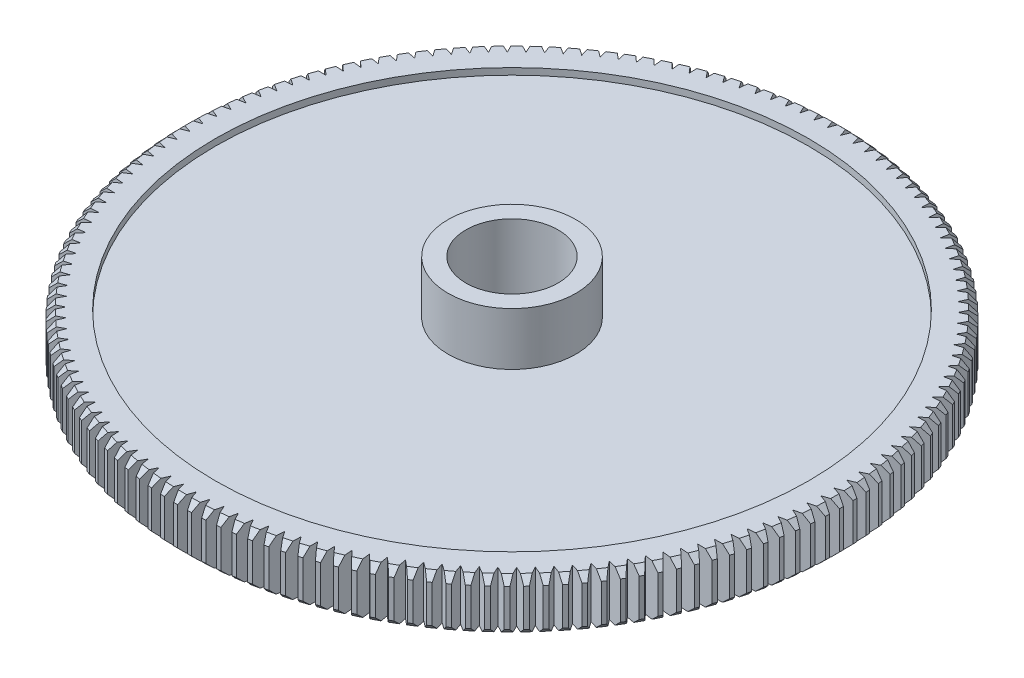
SolidWorks part; units mm, degrees
ref_plane "Спереди" through (0, 0, 0) normal (0, 0, 1) x (1, 0, 0)
ref_plane "Сверху" through (0, 0, 0) normal (0, 1, 0) x (1, 0, 0)
ref_plane "Справа" through (0, 0, 0) normal (1, 0, 0) x (0, 0, -1)
sketch "Эскиз1" plane through (0, 0, 0) normal (0, 1, 0) x (1, 0, 0)
  circle A0 centre (0, 0) radius 25
extrude "Вытянуть1" add sketch "Эскиз1" along normal blind 3.85
chamfer "Фаска2" distance 0.5 angle 45 1 edges at (0, 0, 25)
chamfer "Фаска1" distance 0.5 angle 45 1 edges at (0, 3.85, 25)
sketch "Эскиз2" plane through (0, 3.85, 0) normal (0, 1, 0) x (1, 0, 0)
  line L0 (0.5624, 25.354) -> (1.5615, 25.3121)
  line L1 (-0.5, 25.3553) -> (0.5, 25.3553)
  line L2 (-0.5, 25.3553) -> (0, 23.9335)
  line L3 (0, 23.9335) -> (0.5, 25.3553)
  line L4 (0.5624, 25.354) -> (1.0024, 23.9125)
  line L5 (1.0024, 23.9125) -> (1.5615, 25.3121)
  line L6 (1.6238, 25.3082) -> (2.6203, 25.2245)
  line L7 (1.6238, 25.3082) -> (2.0031, 23.8495)
  line L8 (2.0031, 23.8495) -> (2.6203, 25.2245)
  line L9 (2.6824, 25.218) -> (3.6745, 25.0926)
  line L10 (2.6824, 25.218) -> (3.0002, 23.7447)
  line L11 (3.0002, 23.7447) -> (3.6745, 25.0926)
  line L12 (3.7363, 25.0835) -> (4.7223, 24.9168)
  line L13 (3.7363, 25.0835) -> (3.9921, 23.5982)
  line L14 (3.9921, 23.5982) -> (4.7223, 24.9168)
  line L15 (4.7836, 24.9051) -> (5.7617, 24.6972)
  line L16 (4.7836, 24.9051) -> (4.977, 23.4103)
  line L17 (4.977, 23.4103) -> (5.7617, 24.6972)
  line L18 (5.8225, 24.6829) -> (6.7911, 24.4342)
  line L19 (5.8225, 24.6829) -> (5.9532, 23.1814)
  line L20 (5.9532, 23.1814) -> (6.7911, 24.4342)
  line L21 (6.8512, 24.4174) -> (7.8085, 24.1284)
  line L22 (6.8512, 24.4174) -> (6.9189, 22.9118)
  line L23 (6.9189, 22.9118) -> (7.8085, 24.1284)
  line L24 (7.8679, 24.1091) -> (8.8122, 23.7802)
  line L25 (7.8679, 24.1091) -> (7.8725, 22.6019)
  line L26 (7.8725, 22.6019) -> (8.8122, 23.7802)
  line L27 (8.8708, 23.7585) -> (9.8005, 23.3904)
  line L28 (8.8708, 23.7585) -> (8.8122, 22.2524)
  line L29 (8.8122, 22.2524) -> (9.8005, 23.3904)
  line L30 (9.8581, 23.3662) -> (10.7716, 22.9594)
  line L31 (9.8581, 23.3662) -> (9.7365, 21.8639)
  line L32 (9.7365, 21.8639) -> (10.7716, 22.9594)
  line L33 (10.8281, 22.9329) -> (11.7238, 22.4882)
  line L34 (10.8281, 22.9329) -> (10.6438, 21.437)
  line L35 (10.6438, 21.437) -> (11.7238, 22.4882)
  line L36 (11.7791, 22.4593) -> (12.6554, 21.9775)
  line L37 (11.7791, 22.4593) -> (11.5323, 20.9725)
  line L38 (11.5323, 20.9725) -> (12.6554, 21.9775)
  line L39 (12.7095, 21.9463) -> (13.5648, 21.4283)
  line L40 (12.7095, 21.9463) -> (12.4006, 20.4711)
  line L41 (12.4006, 20.4711) -> (13.5648, 21.4283)
  line L42 (13.6175, 21.3949) -> (14.4505, 20.8415)
  line L43 (13.6175, 21.3949) -> (13.2472, 19.9339)
  line L44 (13.2472, 19.9339) -> (14.4505, 20.8415)
  line L45 (14.5017, 20.8058) -> (15.3107, 20.2181)
  line L46 (14.5017, 20.8058) -> (14.0705, 19.3617)
  line L47 (14.0705, 19.3617) -> (15.3107, 20.2181)
  line L48 (15.3605, 20.1803) -> (16.1442, 19.5592)
  line L49 (15.3605, 20.1803) -> (14.8691, 18.7555)
  line L50 (14.8691, 18.7555) -> (16.1442, 19.5592)
  line L51 (16.1922, 19.5194) -> (16.9492, 18.866)
  line L52 (16.1922, 19.5194) -> (15.6417, 18.1164)
  line L53 (15.6417, 18.1164) -> (16.9492, 18.866)
  line L54 (16.9956, 18.8242) -> (17.7246, 18.1397)
  line L55 (16.9956, 18.8242) -> (16.3868, 17.4455)
  line L56 (16.3868, 17.4455) -> (17.7246, 18.1397)
  line L57 (17.7692, 18.096) -> (18.4689, 17.3815)
  line L58 (17.7692, 18.096) -> (17.1032, 16.7439)
  line L59 (17.1032, 16.7439) -> (18.4689, 17.3815)
  line L60 (18.5116, 17.336) -> (19.1807, 16.5929)
  line L61 (18.5116, 17.336) -> (17.7895, 16.013)
  line L62 (17.7895, 16.013) -> (19.1807, 16.5929)
  line L63 (19.2215, 16.5456) -> (19.8589, 15.7751)
  line L64 (19.2215, 16.5456) -> (18.4447, 15.254)
  line L65 (18.4447, 15.254) -> (19.8589, 15.7751)
  line L66 (19.8977, 15.7262) -> (20.5023, 14.9297)
  line L67 (19.8977, 15.7262) -> (19.0675, 14.4683)
  line L68 (19.0675, 14.4683) -> (20.5023, 14.9297)
  line L69 (20.539, 14.8792) -> (21.1097, 14.058)
  line L70 (20.539, 14.8792) -> (19.6568, 13.6571)
  line L71 (19.6568, 13.6571) -> (21.1097, 14.058)
  line L72 (21.1442, 14.006) -> (21.6801, 13.1617)
  line L73 (21.1442, 14.006) -> (20.2117, 12.822)
  line L74 (20.2117, 12.822) -> (21.6801, 13.1617)
  line L75 (21.7124, 13.1083) -> (22.2124, 12.2423)
  line L76 (21.7124, 13.1083) -> (20.7311, 11.9644)
  line L77 (20.7311, 11.9644) -> (22.2124, 12.2423)
  line L78 (22.2425, 12.1876) -> (22.7058, 11.3014)
  line L79 (22.2425, 12.1876) -> (21.2141, 11.0857)
  line L80 (21.2141, 11.0857) -> (22.7058, 11.3014)
  line L81 (22.7335, 11.2455) -> (23.1593, 10.3406)
  line L82 (22.7335, 11.2455) -> (21.6599, 10.1877)
  line L83 (21.6599, 10.1877) -> (23.1593, 10.3406)
  line L84 (23.1847, 10.2836) -> (23.5722, 9.3617)
  line L85 (23.1847, 10.2836) -> (22.0677, 9.2717)
  line L86 (22.0677, 9.2717) -> (23.5722, 9.3617)
  line L87 (23.5952, 9.3037) -> (23.9438, 8.3664)
  line L88 (23.5952, 9.3037) -> (22.4368, 8.3395)
  line L89 (22.4368, 8.3395) -> (23.9438, 8.3664)
  line L90 (23.9643, 8.3075) -> (24.2733, 7.3564)
  line L91 (23.9643, 8.3075) -> (22.7666, 7.3926)
  line L92 (22.7666, 7.3926) -> (24.2733, 7.3564)
  line L93 (24.2913, 7.2967) -> (24.5603, 6.3335)
  line L94 (24.2913, 7.2967) -> (23.0563, 6.4327)
  line L95 (23.0563, 6.4327) -> (24.5603, 6.3335)
  line L96 (24.5758, 6.2731) -> (24.8041, 5.2995)
  line L97 (24.5758, 6.2731) -> (23.3057, 5.4616)
  line L98 (23.3057, 5.4616) -> (24.8041, 5.2995)
  line L99 (24.8171, 5.2384) -> (25.0045, 4.2561)
  line L100 (24.8171, 5.2384) -> (23.5142, 4.4809)
  line L101 (23.5142, 4.4809) -> (25.0045, 4.2561)
  line L102 (25.0149, 4.1946) -> (25.161, 3.2053)
  line L103 (25.0149, 4.1946) -> (23.6814, 3.4922)
  line L104 (23.6814, 3.4922) -> (25.161, 3.2053)
  line L105 (25.1688, 3.1434) -> (25.2733, 2.1489)
  line L106 (25.1688, 3.1434) -> (23.807, 2.4975)
  line L107 (23.807, 2.4975) -> (25.2733, 2.1489)
  line L108 (25.2786, 2.0867) -> (25.3414, 1.0886)
  line L109 (25.2786, 2.0867) -> (23.8909, 1.4984)
  line L110 (23.8909, 1.4984) -> (25.3414, 1.0886)
  line L111 (25.344, 1.0263) -> (25.3649, 0.0265)
  line L112 (25.344, 1.0263) -> (23.9329, 0.4966)
  line L113 (23.9329, 0.4966) -> (25.3649, 0.0265)
  line L114 (25.3649, -0.0359) -> (25.344, -1.0357)
  line L115 (25.3649, -0.0359) -> (23.9329, -0.506)
  line L116 (23.9329, -0.506) -> (25.344, -1.0357)
  line L117 (25.3414, -1.0981) -> (25.2786, -2.0961)
  line L118 (25.3414, -1.0981) -> (23.8909, -1.5078)
  line L119 (23.8909, -1.5078) -> (25.2786, -2.0961)
  line L120 (25.2733, -2.1583) -> (25.1688, -3.1528)
  line L121 (25.2733, -2.1583) -> (23.807, -2.5069)
  line L122 (23.807, -2.5069) -> (25.1688, -3.1528)
  line L123 (25.161, -3.2147) -> (25.0149, -4.204)
  line L124 (25.161, -3.2147) -> (23.6814, -3.5017)
  line L125 (23.6814, -3.5017) -> (25.0149, -4.204)
  line L126 (25.0045, -4.2656) -> (24.8171, -5.2478)
  line L127 (25.0045, -4.2656) -> (23.5142, -4.4903)
  line L128 (23.5142, -4.4903) -> (24.8171, -5.2478)
  line L129 (24.8041, -5.3089) -> (24.5758, -6.2825)
  line L130 (24.8041, -5.3089) -> (23.3057, -5.471)
  line L131 (23.3057, -5.471) -> (24.5758, -6.2825)
  line L132 (24.5603, -6.3429) -> (24.2913, -7.3061)
  line L133 (24.5603, -6.3429) -> (23.0563, -6.4422)
  line L134 (23.0563, -6.4422) -> (24.2913, -7.3061)
  line L135 (24.2733, -7.3659) -> (23.9643, -8.3169)
  line L136 (24.2733, -7.3659) -> (22.7666, -7.402)
  line L137 (22.7666, -7.402) -> (23.9643, -8.3169)
  line L138 (23.9438, -8.3759) -> (23.5952, -9.3131)
  line L139 (23.9438, -8.3759) -> (22.4368, -8.3489)
  line L140 (22.4368, -8.3489) -> (23.5952, -9.3131)
  line L141 (23.5722, -9.3712) -> (23.1847, -10.293)
  line L142 (23.5722, -9.3712) -> (22.0677, -9.2811)
  line L143 (22.0677, -9.2811) -> (23.1847, -10.293)
  line L144 (23.1593, -10.3501) -> (22.7335, -11.2549)
  line L145 (23.1593, -10.3501) -> (21.6599, -10.1971)
  line L146 (21.6599, -10.1971) -> (22.7335, -11.2549)
  line L147 (22.7058, -11.3108) -> (22.2425, -12.197)
  line L148 (22.7058, -11.3108) -> (21.2141, -11.0952)
  line L149 (21.2141, -11.0952) -> (22.2425, -12.197)
  line L150 (22.2124, -12.2517) -> (21.7124, -13.1177)
  line L151 (22.2124, -12.2517) -> (20.7311, -11.9738)
  line L152 (20.7311, -11.9738) -> (21.7124, -13.1177)
  line L153 (21.6801, -13.1711) -> (21.1442, -14.0154)
  line L154 (21.6801, -13.1711) -> (20.2117, -12.8314)
  line L155 (20.2117, -12.8314) -> (21.1442, -14.0154)
  line L156 (21.1097, -14.0674) -> (20.539, -14.8886)
  line L157 (21.1097, -14.0674) -> (19.6568, -13.6666)
  line L158 (19.6568, -13.6666) -> (20.539, -14.8886)
  line L159 (20.5023, -14.9391) -> (19.8977, -15.7356)
  line L160 (20.5023, -14.9391) -> (19.0675, -14.4777)
  line L161 (19.0675, -14.4777) -> (19.8977, -15.7356)
  line L162 (19.8589, -15.7845) -> (19.2215, -16.555)
  line L163 (19.8589, -15.7845) -> (18.4447, -15.2635)
  line L164 (18.4447, -15.2635) -> (19.2215, -16.555)
  line L165 (19.1807, -16.6023) -> (18.5116, -17.3454)
  line L166 (19.1807, -16.6023) -> (17.7895, -16.0225)
  line L167 (17.7895, -16.0225) -> (18.5116, -17.3454)
  line L168 (18.4689, -17.3909) -> (17.7692, -18.1054)
  line L169 (18.4689, -17.3909) -> (17.1032, -16.7534)
  line L170 (17.1032, -16.7534) -> (17.7692, -18.1054)
  line L171 (17.7246, -18.1491) -> (16.9956, -18.8336)
  line L172 (17.7246, -18.1491) -> (16.3868, -17.4549)
  line L173 (16.3868, -17.4549) -> (16.9956, -18.8336)
  line L174 (16.9492, -18.8754) -> (16.1922, -19.5288)
  line L175 (16.9492, -18.8754) -> (15.6417, -18.1258)
  line L176 (15.6417, -18.1258) -> (16.1922, -19.5288)
  line L177 (16.1442, -19.5686) -> (15.3605, -20.1898)
  line L178 (16.1442, -19.5686) -> (14.8691, -18.7649)
  line L179 (14.8691, -18.7649) -> (15.3605, -20.1898)
  line L180 (15.3107, -20.2275) -> (14.5017, -20.8153)
  line L181 (15.3107, -20.2275) -> (14.0705, -19.3711)
  line L182 (14.0705, -19.3711) -> (14.5017, -20.8153)
  line L183 (14.4505, -20.8509) -> (13.6175, -21.4043)
  line L184 (14.4505, -20.8509) -> (13.2472, -19.9433)
  line L185 (13.2472, -19.9433) -> (13.6175, -21.4043)
  line L186 (13.5648, -21.4377) -> (12.7095, -21.9558)
  line L187 (13.5648, -21.4377) -> (12.4006, -20.4806)
  line L188 (12.4006, -20.4806) -> (12.7095, -21.9558)
  line L189 (12.6554, -21.987) -> (11.7791, -22.4687)
  line L190 (12.6554, -21.987) -> (11.5323, -20.9819)
  line L191 (11.5323, -20.9819) -> (11.7791, -22.4687)
  line L192 (11.7238, -22.4976) -> (10.8281, -22.9423)
  line L193 (11.7238, -22.4976) -> (10.6438, -21.4464)
  line L194 (10.6438, -21.4464) -> (10.8281, -22.9423)
  line L195 (10.7716, -22.9689) -> (9.8581, -23.3756)
  line L196 (10.7716, -22.9689) -> (9.7365, -21.8733)
  line L197 (9.7365, -21.8733) -> (9.8581, -23.3756)
  line L198 (9.8005, -23.3998) -> (8.8708, -23.7679)
  line L199 (9.8005, -23.3998) -> (8.8122, -22.2619)
  line L200 (8.8122, -22.2619) -> (8.8708, -23.7679)
  line L201 (8.8122, -23.7897) -> (7.8679, -24.1185)
  line L202 (8.8122, -23.7897) -> (7.8725, -22.6114)
  line L203 (7.8725, -22.6114) -> (7.8679, -24.1185)
  line L204 (7.8085, -24.1378) -> (6.8512, -24.4269)
  line L205 (7.8085, -24.1378) -> (6.9189, -22.9212)
  line L206 (6.9189, -22.9212) -> (6.8512, -24.4269)
  line L207 (6.7911, -24.4436) -> (5.8225, -24.6923)
  line L208 (6.7911, -24.4436) -> (5.9532, -23.1908)
  line L209 (5.9532, -23.1908) -> (5.8225, -24.6923)
  line L210 (5.7617, -24.7066) -> (4.7836, -24.9145)
  line L211 (5.7617, -24.7066) -> (4.977, -23.4198)
  line L212 (4.977, -23.4198) -> (4.7836, -24.9145)
  line L213 (4.7223, -24.9262) -> (3.7363, -25.093)
  line L214 (4.7223, -24.9262) -> (3.9921, -23.6077)
  line L215 (3.9921, -23.6077) -> (3.7363, -25.093)
  line L216 (3.6745, -25.1021) -> (2.6824, -25.2274)
  line L217 (3.6745, -25.1021) -> (3.0002, -23.7541)
  line L218 (3.0002, -23.7541) -> (2.6824, -25.2274)
  line L219 (2.6203, -25.2339) -> (1.6238, -25.3176)
  line L220 (2.6203, -25.2339) -> (2.0031, -23.8589)
  line L221 (2.0031, -23.8589) -> (1.6238, -25.3176)
  line L222 (1.5615, -25.3215) -> (0.5624, -25.3634)
  line L223 (1.5615, -25.3215) -> (1.0024, -23.9219)
  line L224 (1.0024, -23.9219) -> (0.5624, -25.3634)
  line L225 (0.5, -25.3647) -> (-0.5, -25.3647)
  line L226 (0.5, -25.3647) -> (0, -23.9429)
  line L227 (0, -23.9429) -> (-0.5, -25.3647)
  line L228 (-0.5624, -25.3634) -> (-1.5615, -25.3215)
  line L229 (-0.5624, -25.3634) -> (-1.0024, -23.9219)
  line L230 (-1.0024, -23.9219) -> (-1.5615, -25.3215)
  line L231 (-1.6238, -25.3176) -> (-2.6203, -25.2339)
  line L232 (-1.6238, -25.3176) -> (-2.0031, -23.8589)
  line L233 (-2.0031, -23.8589) -> (-2.6203, -25.2339)
  line L234 (-2.6824, -25.2274) -> (-3.6745, -25.1021)
  line L235 (-2.6824, -25.2274) -> (-3.0002, -23.7541)
  line L236 (-3.0002, -23.7541) -> (-3.6745, -25.1021)
  line L237 (-3.7363, -25.093) -> (-4.7223, -24.9262)
  line L238 (-3.7363, -25.093) -> (-3.9921, -23.6077)
  line L239 (-3.9921, -23.6077) -> (-4.7223, -24.9262)
  line L240 (-4.7836, -24.9145) -> (-5.7617, -24.7066)
  line L241 (-4.7836, -24.9145) -> (-4.977, -23.4198)
  line L242 (-4.977, -23.4198) -> (-5.7617, -24.7066)
  line L243 (-5.8225, -24.6923) -> (-6.7911, -24.4436)
  line L244 (-5.8225, -24.6923) -> (-5.9532, -23.1908)
  line L245 (-5.9532, -23.1908) -> (-6.7911, -24.4436)
  line L246 (-6.8512, -24.4269) -> (-7.8085, -24.1378)
  line L247 (-6.8512, -24.4269) -> (-6.9189, -22.9212)
  line L248 (-6.9189, -22.9212) -> (-7.8085, -24.1378)
  line L249 (-7.8679, -24.1185) -> (-8.8122, -23.7897)
  line L250 (-7.8679, -24.1185) -> (-7.8725, -22.6114)
  line L251 (-7.8725, -22.6114) -> (-8.8122, -23.7897)
  line L252 (-8.8708, -23.7679) -> (-9.8005, -23.3998)
  line L253 (-8.8708, -23.7679) -> (-8.8122, -22.2619)
  line L254 (-8.8122, -22.2619) -> (-9.8005, -23.3998)
  line L255 (-9.8581, -23.3756) -> (-10.7716, -22.9689)
  line L256 (-9.8581, -23.3756) -> (-9.7365, -21.8733)
  line L257 (-9.7365, -21.8733) -> (-10.7716, -22.9689)
  line L258 (-10.8281, -22.9423) -> (-11.7238, -22.4976)
  line L259 (-10.8281, -22.9423) -> (-10.6438, -21.4464)
  line L260 (-10.6438, -21.4464) -> (-11.7238, -22.4976)
  line L261 (-11.7791, -22.4687) -> (-12.6554, -21.987)
  line L262 (-11.7791, -22.4687) -> (-11.5323, -20.9819)
  line L263 (-11.5323, -20.9819) -> (-12.6554, -21.987)
  line L264 (-12.7095, -21.9558) -> (-13.5648, -21.4377)
  line L265 (-12.7095, -21.9558) -> (-12.4006, -20.4806)
  line L266 (-12.4006, -20.4806) -> (-13.5648, -21.4377)
  line L267 (-13.6175, -21.4043) -> (-14.4505, -20.8509)
  line L268 (-13.6175, -21.4043) -> (-13.2472, -19.9433)
  line L269 (-13.2472, -19.9433) -> (-14.4505, -20.8509)
  line L270 (-14.5017, -20.8153) -> (-15.3107, -20.2275)
  line L271 (-14.5017, -20.8153) -> (-14.0705, -19.3711)
  line L272 (-14.0705, -19.3711) -> (-15.3107, -20.2275)
  line L273 (-15.3605, -20.1898) -> (-16.1442, -19.5686)
  line L274 (-15.3605, -20.1898) -> (-14.8691, -18.7649)
  line L275 (-14.8691, -18.7649) -> (-16.1442, -19.5686)
  line L276 (-16.1922, -19.5288) -> (-16.9492, -18.8754)
  line L277 (-16.1922, -19.5288) -> (-15.6417, -18.1258)
  line L278 (-15.6417, -18.1258) -> (-16.9492, -18.8754)
  line L279 (-16.9956, -18.8336) -> (-17.7246, -18.1491)
  line L280 (-16.9956, -18.8336) -> (-16.3868, -17.4549)
  line L281 (-16.3868, -17.4549) -> (-17.7246, -18.1491)
  line L282 (-17.7692, -18.1054) -> (-18.4689, -17.3909)
  line L283 (-17.7692, -18.1054) -> (-17.1032, -16.7534)
  line L284 (-17.1032, -16.7534) -> (-18.4689, -17.3909)
  line L285 (-18.5116, -17.3454) -> (-19.1807, -16.6023)
  line L286 (-18.5116, -17.3454) -> (-17.7895, -16.0225)
  line L287 (-17.7895, -16.0225) -> (-19.1807, -16.6023)
  line L288 (-19.2215, -16.555) -> (-19.8589, -15.7845)
  line L289 (-19.2215, -16.555) -> (-18.4447, -15.2635)
  line L290 (-18.4447, -15.2635) -> (-19.8589, -15.7845)
  line L291 (-19.8977, -15.7356) -> (-20.5023, -14.9391)
  line L292 (-19.8977, -15.7356) -> (-19.0675, -14.4777)
  line L293 (-19.0675, -14.4777) -> (-20.5023, -14.9391)
  line L294 (-20.539, -14.8886) -> (-21.1097, -14.0674)
  line L295 (-20.539, -14.8886) -> (-19.6568, -13.6666)
  line L296 (-19.6568, -13.6666) -> (-21.1097, -14.0674)
  line L297 (-21.1442, -14.0154) -> (-21.6801, -13.1711)
  line L298 (-21.1442, -14.0154) -> (-20.2117, -12.8314)
  line L299 (-20.2117, -12.8314) -> (-21.6801, -13.1711)
  line L300 (-21.7124, -13.1177) -> (-22.2124, -12.2517)
  line L301 (-21.7124, -13.1177) -> (-20.7311, -11.9738)
  line L302 (-20.7311, -11.9738) -> (-22.2124, -12.2517)
  line L303 (-22.2425, -12.197) -> (-22.7058, -11.3108)
  line L304 (-22.2425, -12.197) -> (-21.2141, -11.0952)
  line L305 (-21.2141, -11.0952) -> (-22.7058, -11.3108)
  line L306 (-22.7335, -11.2549) -> (-23.1593, -10.3501)
  line L307 (-22.7335, -11.2549) -> (-21.6599, -10.1971)
  line L308 (-21.6599, -10.1971) -> (-23.1593, -10.3501)
  line L309 (-23.1847, -10.293) -> (-23.5722, -9.3712)
  line L310 (-23.1847, -10.293) -> (-22.0677, -9.2811)
  line L311 (-22.0677, -9.2811) -> (-23.5722, -9.3712)
  line L312 (-23.5952, -9.3131) -> (-23.9438, -8.3759)
  line L313 (-23.5952, -9.3131) -> (-22.4368, -8.3489)
  line L314 (-22.4368, -8.3489) -> (-23.9438, -8.3759)
  line L315 (-23.9643, -8.3169) -> (-24.2733, -7.3659)
  line L316 (-23.9643, -8.3169) -> (-22.7666, -7.402)
  line L317 (-22.7666, -7.402) -> (-24.2733, -7.3659)
  line L318 (-24.2913, -7.3061) -> (-24.5603, -6.3429)
  line L319 (-24.2913, -7.3061) -> (-23.0563, -6.4422)
  line L320 (-23.0563, -6.4422) -> (-24.5603, -6.3429)
  line L321 (-24.5758, -6.2825) -> (-24.8041, -5.3089)
  line L322 (-24.5758, -6.2825) -> (-23.3057, -5.471)
  line L323 (-23.3057, -5.471) -> (-24.8041, -5.3089)
  line L324 (-24.8171, -5.2478) -> (-25.0045, -4.2656)
  line L325 (-24.8171, -5.2478) -> (-23.5142, -4.4903)
  line L326 (-23.5142, -4.4903) -> (-25.0045, -4.2656)
  line L327 (-25.0149, -4.204) -> (-25.161, -3.2147)
  line L328 (-25.0149, -4.204) -> (-23.6814, -3.5017)
  line L329 (-23.6814, -3.5017) -> (-25.161, -3.2147)
  line L330 (-25.1688, -3.1528) -> (-25.2733, -2.1583)
  line L331 (-25.1688, -3.1528) -> (-23.807, -2.5069)
  line L332 (-23.807, -2.5069) -> (-25.2733, -2.1583)
  line L333 (-25.2786, -2.0961) -> (-25.3414, -1.0981)
  line L334 (-25.2786, -2.0961) -> (-23.8909, -1.5078)
  line L335 (-23.8909, -1.5078) -> (-25.3414, -1.0981)
  line L336 (-25.344, -1.0357) -> (-25.3649, -0.0359)
  line L337 (-25.344, -1.0357) -> (-23.9329, -0.506)
  line L338 (-23.9329, -0.506) -> (-25.3649, -0.0359)
  line L339 (-25.3649, 0.0265) -> (-25.344, 1.0263)
  line L340 (-25.3649, 0.0265) -> (-23.9329, 0.4966)
  line L341 (-23.9329, 0.4966) -> (-25.344, 1.0263)
  line L342 (-25.3414, 1.0886) -> (-25.2786, 2.0867)
  line L343 (-25.3414, 1.0886) -> (-23.8909, 1.4984)
  line L344 (-23.8909, 1.4984) -> (-25.2786, 2.0867)
  line L345 (-25.2733, 2.1489) -> (-25.1688, 3.1434)
  line L346 (-25.2733, 2.1489) -> (-23.807, 2.4975)
  line L347 (-23.807, 2.4975) -> (-25.1688, 3.1434)
  line L348 (-25.161, 3.2053) -> (-25.0149, 4.1946)
  line L349 (-25.161, 3.2053) -> (-23.6814, 3.4922)
  line L350 (-23.6814, 3.4922) -> (-25.0149, 4.1946)
  line L351 (-25.0045, 4.2561) -> (-24.8171, 5.2384)
  line L352 (-25.0045, 4.2561) -> (-23.5142, 4.4809)
  line L353 (-23.5142, 4.4809) -> (-24.8171, 5.2384)
  line L354 (-24.8041, 5.2995) -> (-24.5758, 6.2731)
  line L355 (-24.8041, 5.2995) -> (-23.3057, 5.4616)
  line L356 (-23.3057, 5.4616) -> (-24.5758, 6.2731)
  line L357 (-24.5603, 6.3335) -> (-24.2913, 7.2967)
  line L358 (-24.5603, 6.3335) -> (-23.0563, 6.4327)
  line L359 (-23.0563, 6.4327) -> (-24.2913, 7.2967)
  line L360 (-24.2733, 7.3564) -> (-23.9643, 8.3075)
  line L361 (-24.2733, 7.3564) -> (-22.7666, 7.3926)
  line L362 (-22.7666, 7.3926) -> (-23.9643, 8.3075)
  line L363 (-23.9438, 8.3664) -> (-23.5952, 9.3037)
  line L364 (-23.9438, 8.3664) -> (-22.4368, 8.3395)
  line L365 (-22.4368, 8.3395) -> (-23.5952, 9.3037)
  line L366 (-23.5722, 9.3617) -> (-23.1847, 10.2836)
  line L367 (-23.5722, 9.3617) -> (-22.0677, 9.2717)
  line L368 (-22.0677, 9.2717) -> (-23.1847, 10.2836)
  line L369 (-23.1593, 10.3406) -> (-22.7335, 11.2455)
  line L370 (-23.1593, 10.3406) -> (-21.6599, 10.1877)
  line L371 (-21.6599, 10.1877) -> (-22.7335, 11.2455)
  line L372 (-22.7058, 11.3014) -> (-22.2425, 12.1876)
  line L373 (-22.7058, 11.3014) -> (-21.2141, 11.0857)
  line L374 (-21.2141, 11.0857) -> (-22.2425, 12.1876)
  line L375 (-22.2124, 12.2423) -> (-21.7124, 13.1083)
  line L376 (-22.2124, 12.2423) -> (-20.7311, 11.9644)
  line L377 (-20.7311, 11.9644) -> (-21.7124, 13.1083)
  line L378 (-21.6801, 13.1617) -> (-21.1442, 14.006)
  line L379 (-21.6801, 13.1617) -> (-20.2117, 12.822)
  line L380 (-20.2117, 12.822) -> (-21.1442, 14.006)
  line L381 (-21.1097, 14.058) -> (-20.539, 14.8792)
  line L382 (-21.1097, 14.058) -> (-19.6568, 13.6571)
  line L383 (-19.6568, 13.6571) -> (-20.539, 14.8792)
  line L384 (-20.5023, 14.9297) -> (-19.8977, 15.7262)
  line L385 (-20.5023, 14.9297) -> (-19.0675, 14.4683)
  line L386 (-19.0675, 14.4683) -> (-19.8977, 15.7262)
  line L387 (-19.8589, 15.7751) -> (-19.2215, 16.5456)
  line L388 (-19.8589, 15.7751) -> (-18.4447, 15.254)
  line L389 (-18.4447, 15.254) -> (-19.2215, 16.5456)
  line L390 (-19.1807, 16.5929) -> (-18.5116, 17.336)
  line L391 (-19.1807, 16.5929) -> (-17.7895, 16.013)
  line L392 (-17.7895, 16.013) -> (-18.5116, 17.336)
  line L393 (-18.4689, 17.3815) -> (-17.7692, 18.096)
  line L394 (-18.4689, 17.3815) -> (-17.1032, 16.7439)
  line L395 (-17.1032, 16.7439) -> (-17.7692, 18.096)
  line L396 (-17.7246, 18.1397) -> (-16.9956, 18.8242)
  line L397 (-17.7246, 18.1397) -> (-16.3868, 17.4455)
  line L398 (-16.3868, 17.4455) -> (-16.9956, 18.8242)
  line L399 (-16.9492, 18.866) -> (-16.1922, 19.5194)
  line L400 (-16.9492, 18.866) -> (-15.6417, 18.1164)
  line L401 (-15.6417, 18.1164) -> (-16.1922, 19.5194)
  line L402 (-16.1442, 19.5592) -> (-15.3605, 20.1803)
  line L403 (-16.1442, 19.5592) -> (-14.8691, 18.7555)
  line L404 (-14.8691, 18.7555) -> (-15.3605, 20.1803)
  line L405 (-15.3107, 20.2181) -> (-14.5017, 20.8058)
  line L406 (-15.3107, 20.2181) -> (-14.0705, 19.3617)
  line L407 (-14.0705, 19.3617) -> (-14.5017, 20.8058)
  line L408 (-14.4505, 20.8415) -> (-13.6175, 21.3949)
  line L409 (-14.4505, 20.8415) -> (-13.2472, 19.9339)
  line L410 (-13.2472, 19.9339) -> (-13.6175, 21.3949)
  line L411 (-13.5648, 21.4283) -> (-12.7095, 21.9463)
  line L412 (-13.5648, 21.4283) -> (-12.4006, 20.4711)
  line L413 (-12.4006, 20.4711) -> (-12.7095, 21.9463)
  line L414 (-12.6554, 21.9775) -> (-11.7791, 22.4593)
  line L415 (-12.6554, 21.9775) -> (-11.5323, 20.9725)
  line L416 (-11.5323, 20.9725) -> (-11.7791, 22.4593)
  line L417 (-11.7238, 22.4882) -> (-10.8281, 22.9329)
  line L418 (-11.7238, 22.4882) -> (-10.6438, 21.437)
  line L419 (-10.6438, 21.437) -> (-10.8281, 22.9329)
  line L420 (-10.7716, 22.9594) -> (-9.8581, 23.3662)
  line L421 (-10.7716, 22.9594) -> (-9.7365, 21.8639)
  line L422 (-9.7365, 21.8639) -> (-9.8581, 23.3662)
  line L423 (-9.8005, 23.3904) -> (-8.8708, 23.7585)
  line L424 (-9.8005, 23.3904) -> (-8.8122, 22.2524)
  line L425 (-8.8122, 22.2524) -> (-8.8708, 23.7585)
  line L426 (-8.8122, 23.7802) -> (-7.8679, 24.1091)
  line L427 (-8.8122, 23.7802) -> (-7.8725, 22.6019)
  line L428 (-7.8725, 22.6019) -> (-7.8679, 24.1091)
  line L429 (-7.8085, 24.1284) -> (-6.8512, 24.4174)
  line L430 (-7.8085, 24.1284) -> (-6.9189, 22.9118)
  line L431 (-6.9189, 22.9118) -> (-6.8512, 24.4174)
  line L432 (-6.7911, 24.4342) -> (-5.8225, 24.6829)
  line L433 (-6.7911, 24.4342) -> (-5.9532, 23.1814)
  line L434 (-5.9532, 23.1814) -> (-5.8225, 24.6829)
  line L435 (-5.7617, 24.6972) -> (-4.7836, 24.9051)
  line L436 (-5.7617, 24.6972) -> (-4.977, 23.4103)
  line L437 (-4.977, 23.4103) -> (-4.7836, 24.9051)
  line L438 (-4.7223, 24.9168) -> (-3.7363, 25.0835)
  line L439 (-4.7223, 24.9168) -> (-3.9921, 23.5982)
  line L440 (-3.9921, 23.5982) -> (-3.7363, 25.0835)
  line L441 (-3.6745, 25.0926) -> (-2.6824, 25.218)
  line L442 (-3.6745, 25.0926) -> (-3.0002, 23.7447)
  line L443 (-3.0002, 23.7447) -> (-2.6824, 25.218)
  line L444 (-2.6203, 25.2245) -> (-1.6238, 25.3082)
  line L445 (-2.6203, 25.2245) -> (-2.0031, 23.8495)
  line L446 (-2.0031, 23.8495) -> (-1.6238, 25.3082)
  line L447 (-1.5615, 25.3121) -> (-0.5624, 25.354)
  line L448 (-1.5615, 25.3121) -> (-1.0024, 23.9125)
  line L449 (-1.0024, 23.9125) -> (-0.5624, 25.354)
extrude "Вытянуть2" cut sketch "Эскиз2" against normal through all
sketch "Эскиз3" plane through (0, 3.85, 0) normal (0, 1, 0) x (-1, 0, 0)
  circle A0 centre (0, 0) radius 22.5
extrude "Вытянуть3" cut sketch "Эскиз3" against normal blind 0.5
sketch "Эскиз4" plane through (0, 0, 0) normal (0, -1, 0) x (1, 0, 0)
  circle A0 centre (0, 0) radius 22.5
extrude "Вытянуть4" cut sketch "Эскиз4" against normal blind 0.5
sketch "Эскиз5" plane through (0, 3.35, 0) normal (0, 1, 0) x (1, 0, 0)
  circle A0 centre (0, 0) radius 3.5
extrude "Вытянуть5" cut sketch "Эскиз5" against normal through all
sketch "Эскиз7" plane through (0, 3.35, 0) normal (0, 1, 0) x (1, 0, 0)
  circle A0 centre (0, 0) radius 3.5
  circle A1 centre (0, 0) radius 4.85
extrude "Вытянуть6" add sketch "Эскиз7" along normal blind 4
sketch "Эскиз8" plane through (0, 0.5, 0) normal (0, -1, 0) x (1, 0, 0)
  circle A0 centre (0, 0) radius 3.5
  circle A1 centre (0, 0) radius 6.92
extrude "Вытянуть7" add sketch "Эскиз8" along normal blind 9
